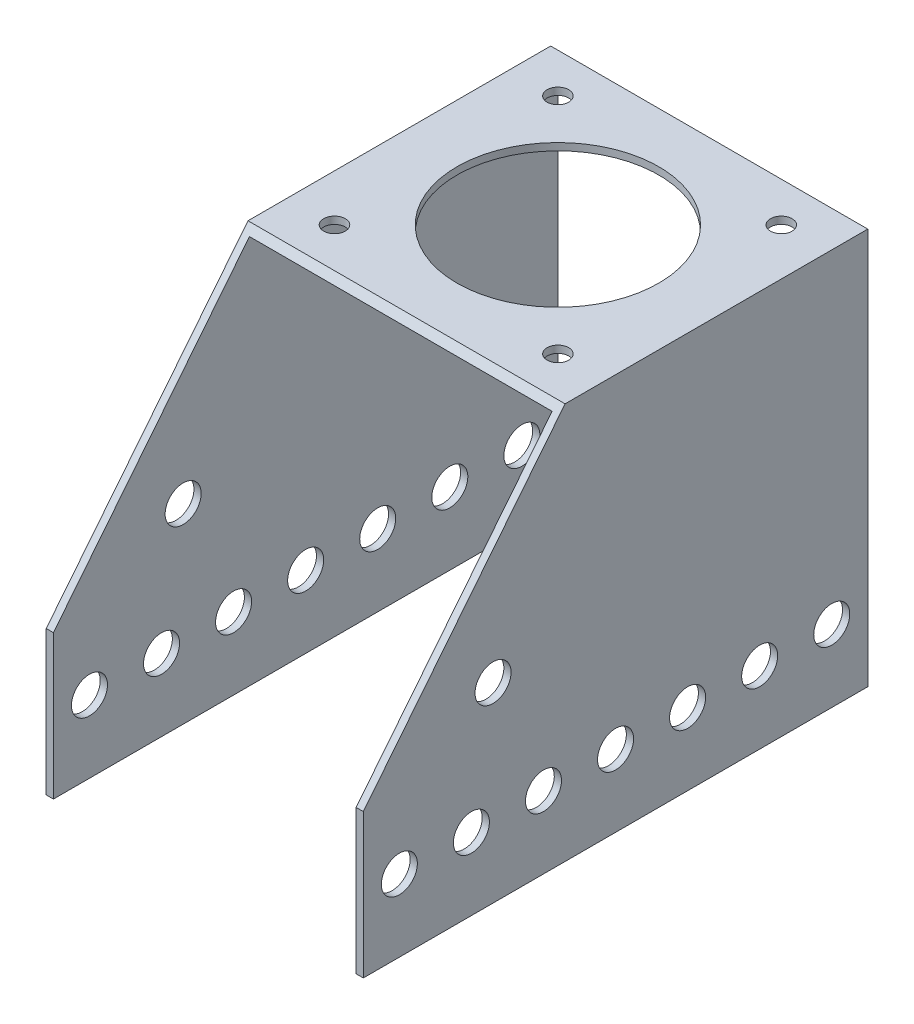
SolidWorks part; units mm, degrees
ref_plane "Front Plane" through (0, 0, 0) normal (0, 0, 1) x (1, 0, 0)
ref_plane "Top Plane" through (0, 0, 0) normal (0, 1, 0) x (1, 0, 0)
ref_plane "Right Plane" through (0, 0, 0) normal (1, 0, 0) x (0, 0, -1)
sketch "Sketch1" plane through (0, 0, 0) normal (0, 0, 1) x (1, 0, 0)
  line L0 (-21, -27.5) -> (-21, 26.5)
  line L1 (-22, -27.5) -> (-21, -27.5)
  line L2 (-22, -27.5) -> (-22, 27.5)
  line L3 (-22, 27.5) -> (22, 27.5)
  line L4 (22, -27.5) -> (22, 27.5)
  line L5 (-22, -27.5) -> (22, 27.5) construction
  line L6 (-22, 27.5) -> (22, -27.5) construction
  line L7 (-21, 26.5) -> (21, 26.5)
  line L8 (21, 26.5) -> (21, -27.5)
  line L9 (21, -27.5) -> (22, -27.5)
  point P0 (0, 0)
  point P8 (21.5, -27.5)
  dimension "D1" = 54
  dimension "D2" = 1
  dimension "D3" = 42
  dimension "D4" = 1
extrude "Boss-Extrude1" add sketch "Sketch1" along normal blind 70
sketch "Sketch2" plane through (0, 27.5, 0) normal (0, 1, 0) x (1, 0, 0)
  line L1 (-22, -21) -> (22, -21) construction
  line L2 (-22, -70) -> (-22, 0) construction
  line L4 (0, -21) -> (15.5, -36.5) construction
  line L7 (22, -70) -> (22, 0) construction
  line L8 (22, 0) -> (-22, 0) construction
  circle A0 centre (15.5, -36.5) radius 1.5
  circle A4 centre (0, -21) radius 14
  circle A5 centre (-15.5, -36.5) radius 1.5
  circle A6 centre (-15.5, -5.5) radius 1.5
  circle A7 centre (15.5, -5.5) radius 1.5
  point P19 (0, -21)
  point P24 (0, -21)
  dimension "D2" = 3
  dimension "D4" = 28
  dimension "D3" = 21
  dimension "D5" = 45
  dimension "D6" = 21.9203
  dimension "D1" = 4
extrude "Cut-Extrude1" cut sketch "Sketch2" against normal through all
sketch "Sketch5" plane through (-22, 0, 0) normal (-1, 0, 0) x (0, 0, 1)
  line L0 (70, -7.5) -> (42, 27.5)
  line L1 (70, 27.5) -> (70, -27.5) construction
  line L2 (70, 27.5) -> (0, 27.5) construction
  line L3 (42, 27.5) -> (70, 27.5)
  line L4 (70, 27.5) -> (70, -7.5)
  line L5 (70, -7.5) -> (70, -27.5) construction
  line L6 (5, -17.5) -> (0, -17.5) construction
  line L7 (0, 27.5) -> (0, -27.5) construction
  line L8 (65, -17.5) -> (70, -17.5) construction
  line L9 (5, -17.5) -> (15, -17.5) construction
  circle A0 centre (5, -17.5) radius 2.5
  circle A1 centre (15, -17.5) radius 2.5
  circle A2 centre (25, -17.5) radius 2.5
  circle A3 centre (35, -17.5) radius 2.5
  circle A4 centre (45, -17.5) radius 2.5
  circle A5 centre (55, -17.5) radius 2.5
  circle A6 centre (65, -17.5) radius 2.5
  circle A7 centre (52, -1.0078) radius 2.5
  point P12 (70, -17.5)
  dimension "D6" = 5
  dimension "D7" = 10
  dimension "D1" = 42
  dimension "D2" = 20
  dimension "D4" = 10
  dimension "D5" = 10
  dimension "D3" = 7
extrude "Cut-Extrude3" cut sketch "Sketch5" against normal through all
